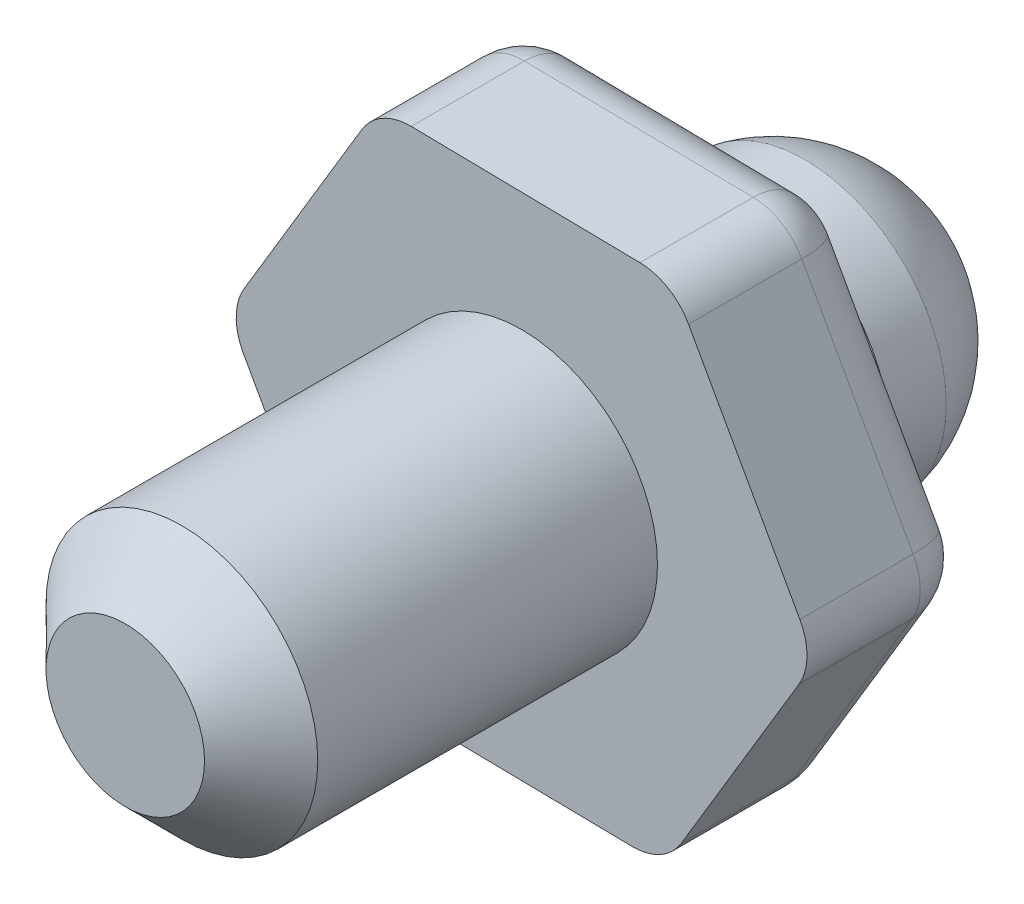
SolidWorks part; units mm, degrees
ref_plane "Front Plane" through (0, 0, 0) normal (0, 0, 1) x (1, 0, 0)
ref_plane "Top Plane" through (0, 0, 0) normal (0, 1, 0) x (1, 0, 0)
ref_plane "Right Plane" through (0, 0, 0) normal (1, 0, 0) x (0, 0, -1)
sketch "Sketch1" plane through (0, 0, 0) normal (0, 0, 1) x (1, 0, 0)
  circle A0 centre (0, 0) radius 3.048
  dimension "D1" = 6.096
extrude "Extrude1" add sketch "Sketch1" along normal blind 8.89
chamfer "Chamfer1" distance 1.27 angle 45 1 edges at (3.048, 0, 8.89)
sketch "Sketch2" plane through (0, 0, 0) normal (0, 0, -1) x (-1, 0, 0)
  line L1 (6.5983, 0.1041) -> (3.209, 5.7663)
  line L2 (3.209, 5.7663) -> (-3.3893, 5.6622)
  line L3 (-3.3893, 5.6622) -> (-6.5983, -0.1041)
  line L4 (-6.5983, -0.1041) -> (-3.209, -5.7663)
  line L5 (-3.209, -5.7663) -> (3.3893, -5.6622)
  line L6 (3.3893, -5.6622) -> (6.5983, 0.1041)
  circle A0 centre (0, 0) radius 5.715 construction
  dimension "D1" = 11.43
extrude "Extrude2" add sketch "Sketch2" along normal blind 3.81
sketch "Sketch3" plane through (0, 0, -3.81) normal (0, 0, -1) x (-1, 0, 0)
  circle A0 centre (0, 0) radius 2.0298
extrude "Extrude3" add sketch "Sketch3" along normal blind 1.27
sketch "Sketch4" plane through (0, 0, -5.08) normal (0, 0, -1) x (-1, 0, 0)
  circle A0 centre (0, 0) radius 3.175
  dimension "D1" = 6.35
extrude "Extrude4" add sketch "Sketch4" along normal blind 1.27
dome "Dome1" faces to dome 1 distance 2.54 reverse direction no elliptical dome no face at (-3.175, 0, -6.35) parameters "D1"=2.54
fillet "Fillet1" radius 1.27 12 edges at (-0.0902, -5.7143, -3.81) (4.9036, -2.9352, -3.81) (4.9938, 2.7791, -3.81) (0.0902, 5.7143, -3.81) (-4.9036, 2.9352, -3.81) (-4.9938, -2.7791, -3.81) (6.5983, -0.1041, -1.905) (3.209, -5.7663, -1.905) (-3.3893, -5.6622, -1.905) (3.3893, 5.6622, -1.905) (-3.209, 5.7663, -1.905) (-6.5983, 0.1041, -1.905)
